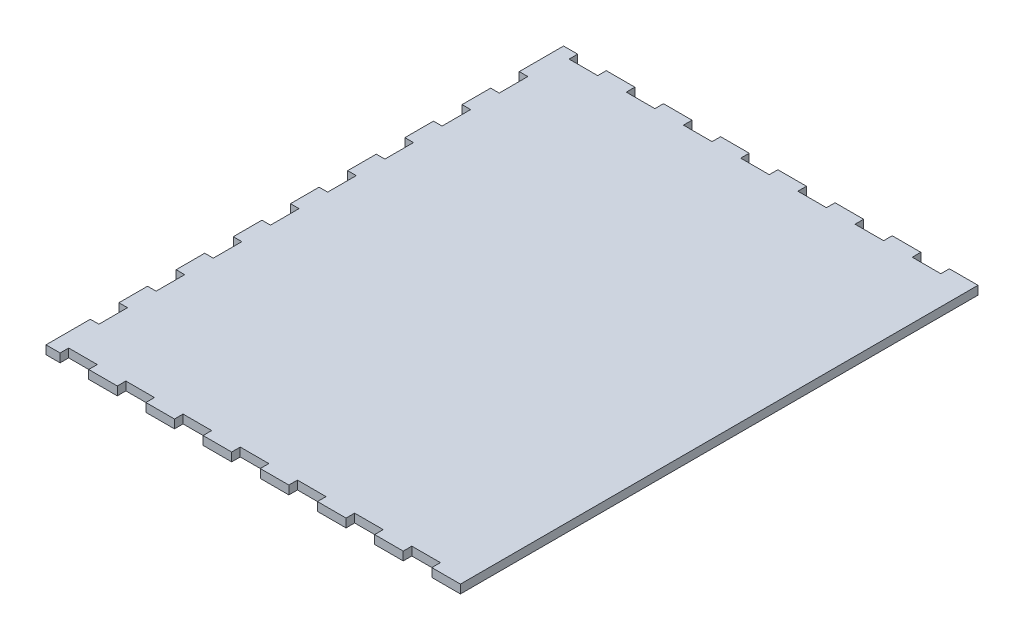
SolidWorks part; units mm, degrees
ref_plane "Front Plane" through (0, 0, 0) normal (0, 0, 1) x (1, 0, 0)
ref_plane "Top Plane" through (0, 0, 0) normal (0, 1, 0) x (1, 0, 0)
ref_plane "Right Plane" through (0, 0, 0) normal (1, 0, 0) x (0, 0, -1)
sketch "Sketch1" plane through (0, 0, 0) normal (0, 1, 0) x (1, 0, 0)
  line L0 (0, 90.5) -> (144.93, 90.5) construction
  line L2 (0, 0) -> (0, 15.5)
  line L3 (0, 181) -> (4.93, 181)
  line L4 (144.93, 0) -> (144.93, 181)
  line L5 (72.465, 181) -> (72.465, 0) construction
  line L6 (134.93, 181) -> (134.93, 178)
  line L7 (134.93, 178) -> (124.93, 178)
  line L8 (124.93, 178) -> (124.93, 181)
  line L9 (134.93, 178) -> (144.93, 178) construction
  line L10 (104.93, 178) -> (104.93, 181)
  line L11 (114.93, 178) -> (104.93, 178)
  line L12 (114.93, 181) -> (114.93, 178)
  line L13 (84.93, 178) -> (84.93, 181)
  line L14 (94.93, 178) -> (84.93, 178)
  line L15 (94.93, 181) -> (94.93, 178)
  line L16 (64.93, 178) -> (64.93, 181)
  line L17 (74.93, 178) -> (64.93, 178)
  line L18 (74.93, 181) -> (74.93, 178)
  line L19 (44.93, 178) -> (44.93, 181)
  line L20 (54.93, 178) -> (44.93, 178)
  line L21 (54.93, 181) -> (54.93, 178)
  line L22 (24.93, 178) -> (24.93, 181)
  line L23 (34.93, 178) -> (24.93, 178)
  line L24 (34.93, 181) -> (34.93, 178)
  line L25 (4.93, 178) -> (4.93, 181)
  line L26 (14.93, 178) -> (4.93, 178)
  line L27 (14.93, 181) -> (14.93, 178)
  line L28 (14.93, 181) -> (24.93, 181)
  line L29 (34.93, 181) -> (44.93, 181)
  line L30 (54.93, 181) -> (64.93, 181)
  line L31 (74.93, 181) -> (84.93, 181)
  line L32 (94.93, 181) -> (104.93, 181)
  line L33 (114.93, 181) -> (124.93, 181)
  line L34 (134.93, 181) -> (144.93, 181)
  line L35 (134.93, 3) -> (144.93, 3) construction
  line L36 (134.93, 0) -> (144.93, 0)
  line L37 (114.93, 0) -> (124.93, 0)
  line L38 (94.93, 0) -> (104.93, 0)
  line L39 (74.93, 0) -> (84.93, 0)
  line L40 (54.93, 0) -> (64.93, 0)
  line L41 (34.93, 0) -> (44.93, 0)
  line L42 (14.93, 0) -> (24.93, 0)
  line L43 (14.93, 0) -> (14.93, 3)
  line L44 (14.93, 3) -> (4.93, 3)
  line L45 (4.93, 3) -> (4.93, 0)
  line L46 (34.93, 0) -> (34.93, 3)
  line L47 (34.93, 3) -> (24.93, 3)
  line L48 (24.93, 3) -> (24.93, 0)
  line L49 (54.93, 0) -> (54.93, 3)
  line L50 (54.93, 3) -> (44.93, 3)
  line L51 (44.93, 3) -> (44.93, 0)
  line L52 (74.93, 0) -> (74.93, 3)
  line L53 (74.93, 3) -> (64.93, 3)
  line L54 (64.93, 3) -> (64.93, 0)
  line L55 (94.93, 0) -> (94.93, 3)
  line L56 (94.93, 3) -> (84.93, 3)
  line L57 (84.93, 3) -> (84.93, 0)
  line L58 (114.93, 0) -> (114.93, 3)
  line L59 (114.93, 3) -> (104.93, 3)
  line L60 (104.93, 3) -> (104.93, 0)
  line L61 (124.93, 3) -> (124.93, 0)
  line L62 (134.93, 3) -> (124.93, 3)
  line L63 (134.93, 0) -> (134.93, 3)
  line L64 (0, 0) -> (4.93, 0)
  line L65 (0, 15.5) -> (3, 15.5)
  line L66 (3, 15.5) -> (3, 25.5)
  line L67 (3, 25.5) -> (0, 25.5)
  line L68 (3, 15.5) -> (3, 0) construction
  line L69 (0, 25.5) -> (0, 35.5)
  line L70 (3, 45.5) -> (0, 45.5)
  line L71 (3, 35.5) -> (3, 45.5)
  line L72 (0, 35.5) -> (3, 35.5)
  line L73 (3, 65.5) -> (0, 65.5)
  line L74 (3, 55.5) -> (3, 65.5)
  line L75 (0, 55.5) -> (3, 55.5)
  line L76 (3, 85.5) -> (0, 85.5)
  line L77 (3, 75.5) -> (3, 85.5)
  line L78 (0, 75.5) -> (3, 75.5)
  line L79 (3, 105.5) -> (0, 105.5)
  line L80 (3, 95.5) -> (3, 105.5)
  line L81 (0, 95.5) -> (3, 95.5)
  line L82 (3, 125.5) -> (0, 125.5)
  line L83 (3, 115.5) -> (3, 125.5)
  line L84 (0, 115.5) -> (3, 115.5)
  line L85 (3, 145.5) -> (0, 145.5)
  line L86 (3, 135.5) -> (3, 145.5)
  line L87 (0, 135.5) -> (3, 135.5)
  line L88 (3, 165.5) -> (0, 165.5)
  line L89 (3, 155.5) -> (3, 165.5)
  line L90 (0, 155.5) -> (3, 155.5)
  line L91 (0, 165.5) -> (0, 181)
  line L92 (0, 145.5) -> (0, 155.5)
  line L93 (0, 125.5) -> (0, 135.5)
  line L94 (0, 105.5) -> (0, 115.5)
  line L95 (0, 45.5) -> (0, 55.5)
  line L96 (0, 65.5) -> (0, 75.5)
  line L97 (0, 85.5) -> (0, 95.5)
  dimension "D1" = 181
  dimension "D2" = 144.93
  dimension "D3" = 10
  dimension "D4" = 10
  dimension "D5" = 3
  dimension "D7" = 15.5
  dimension "D8" = 10
  dimension "D9" = 3
  dimension "D6" = 7
  dimension "D10" = 8
extrude "Boss-Extrude1" add sketch "Sketch1" along normal blind 3
